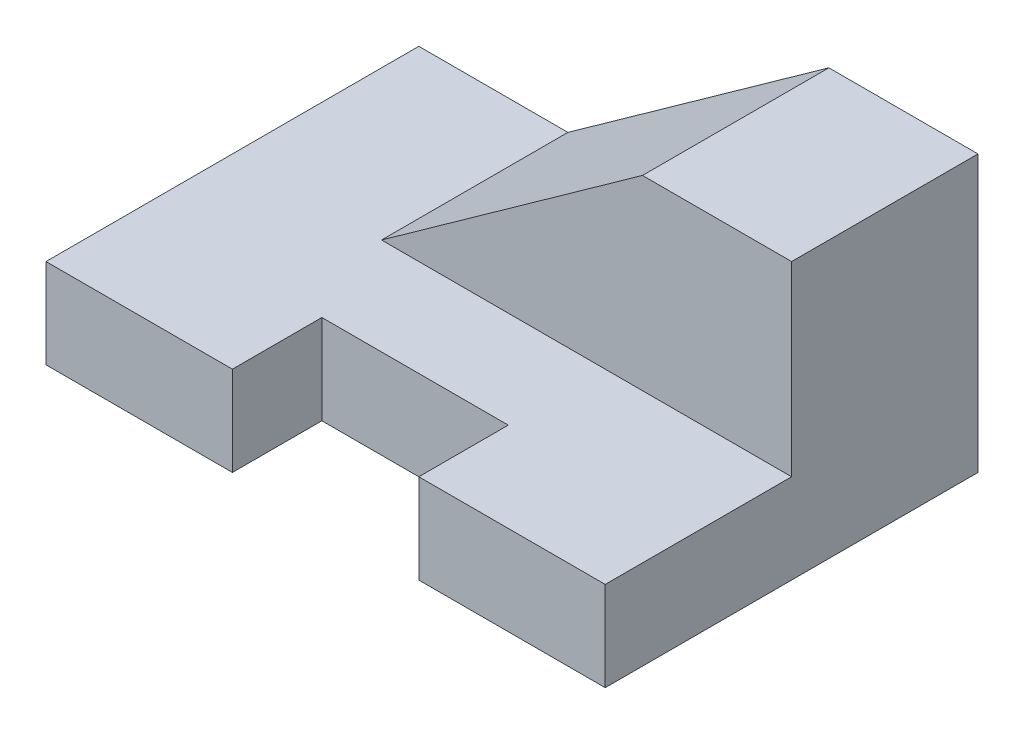
SolidWorks part; units mm, degrees
ref_plane "Front Plane" through (0, 0, 0) normal (0, 0, 1) x (1, 0, 0)
ref_plane "Top Plane" through (0, 0, 0) normal (0, 1, 0) x (1, 0, 0)
ref_plane "Right Plane" through (0, 0, 0) normal (1, 0, 0) x (0, 0, -1)
sketch "Sketch1" plane through (0, 0, 0) normal (0, 0, 1) x (1, 0, 0)
  line L0 (0, 12) -> (0, 37)
  line L1 (0, 0) -> (-75, 0)
  line L2 (0, 0) -> (0, 12)
  line L3 (0, 12) -> (-75, 12)
  line L4 (-75, 0) -> (-75, 12)
  line L5 (0, 37) -> (-20, 37)
  line L6 (-20, 37) -> (-55, 12)
  line L7 (-50, 12) -> (-50, 0)
  line L8 (-25, 12) -> (-25, 0)
  dimension "D1" = 75
  dimension "D2" = 25
  dimension "D3" = 25
  dimension "D4" = 12
  dimension "D5" = 25
  dimension "D6" = 20
  dimension "D7" = 20
extrude "Boss-Extrude1" add sketch "Sketch1" along normal blind 25 contours L5 L6 L3 L0 region at (-20.1111, 22.5556, 0)
extrude "Boss-Extrude2" add sketch "Sketch1<3>" along normal blind 50 contours L7 L3 L4 L1 | L3 L8 L1 L2 region at (-12.5, 6, 0) region at (-62.5, 6, 0)
sketch "Sketch1<3>" plane through (0, 0, 0) normal (0, 0, 1) x (1, 0, 0) same geometry as "Sketch1"
extrude "Boss-Extrude3" add sketch "Sketch1<4>" along normal blind 38 contours L8 L3 L7 L1 region at (-37.5, 6, 0)
sketch "Sketch1<4>" plane through (0, 0, 0) normal (0, 0, 1) x (1, 0, 0) same geometry as "Sketch1"
